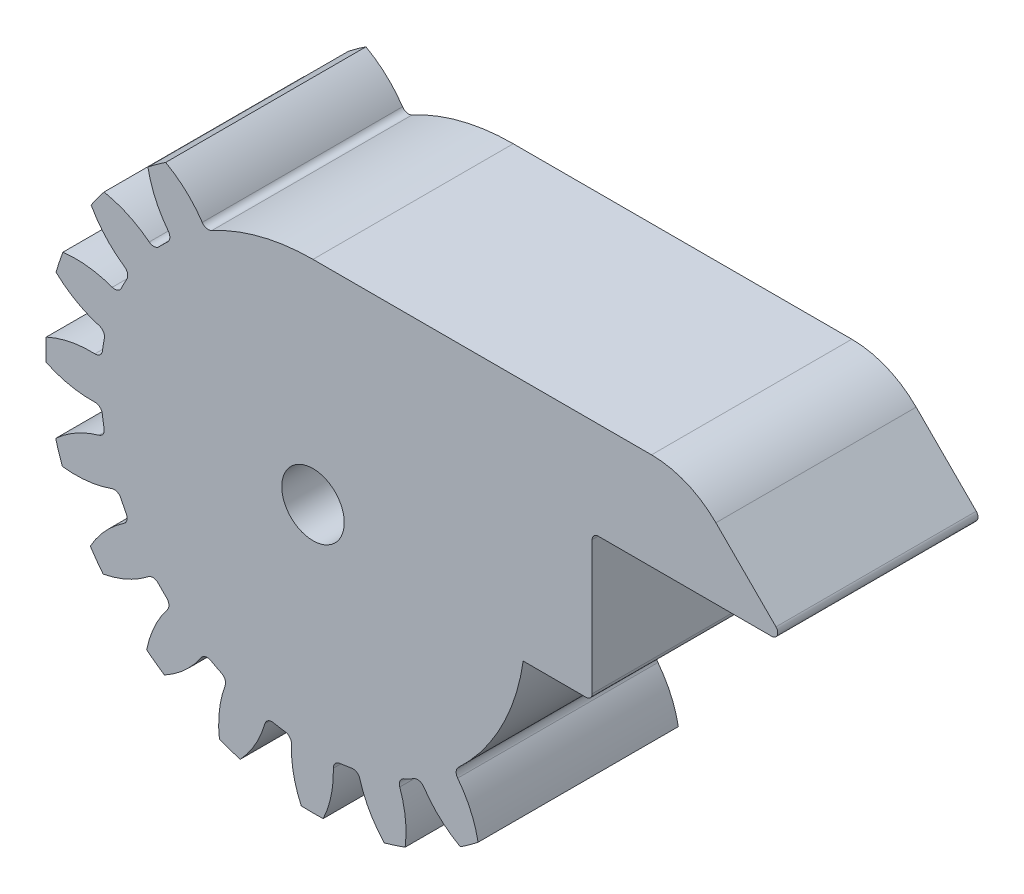
SolidWorks part; units mm, degrees
material "1023 Carbon Steel Sheet (SS)"
ref_plane "Front Plane" through (0, 0, 0) normal (0, 0, 1) x (1, 0, 0)
ref_plane "Top Plane" through (0, 0, 0) normal (0, 1, 0) x (1, 0, 0)
ref_plane "Right Plane" through (0, 0, 0) normal (1, 0, 0) x (0, 0, -1)
sketch "skBase" plane through (0, 0, 0) normal (0, 0, 1) x (1, 0, 0)
  circle A0 centre (0, 0) radius 20
  circle A1 centre (0, 0) radius 22
  circle A2 centre (0, 0) radius 17.5
  dimension "D1" = 40
  dimension "D3" = 4.5
extrude "Base" add sketch "skBase" along normal mid plane 16.5 contours A1
sketch "skToothProfile" plane through (0, 0, 0) normal (0, 0, 1) x (1, 0, 0)
  line L0 (0, 0) -> (0, 22) construction
  line L1 (-1.5692, 19.9383) -> (1.5692, 19.9383) construction
  line L2 (-1.0563, 17.4681) -> (0, 0) construction
  line L3 (0, 15.6271) -> (-2.6287, 22.8493) construction
  line L4 (0, 0) -> (3.4416, 21.7291) construction
  line L5 (1.5692, 19.9383) -> (4.6689, 19.4474) construction
  circle A0 centre (0, 0) radius 22 construction
  arc A1 (-1.0563, 17.4681) -> (-3.258, 22.7681) centre (-9.8105, 16.9387) ccw
  arc A2 (1.0563, 17.4681) -> (3.258, 22.7681) centre (9.8105, 16.9387) cw
  circle A3 centre (0, 0) radius 17.5 construction
  arc A4 (1.0563, 17.4681) -> (-1.0563, 17.4681) centre (0, 0) ccw
  circle A5 centre (0, 0) radius 20 construction
  circle A6 centre (0, 0) radius 22 construction
  circle A7 centre (0, 0) radius 23
  arc A8 (3.258, 22.7681) -> (-3.258, 22.7681) centre (0, 0) ccw
  dimension "D2" = 20
  dimension "D3" = 9
extrude "ToothProfile" cut sketch "skToothProfile" against normal through all and the other way through all
fillet "FilletToothProfile" radius 0.6 2 edges at (1.0563, 17.4681, 0) (-1.0563, 17.4681, 0)
pattern_circular "CirPatternTeeth" count 20 over 360 about axis through (0, 0, 8.25) along (0, 0, 1) of "ToothProfile", "FilletToothProfile"
sketch "skChaveta" plane through (0, 0, 8.25) normal (0, 0, 1) x (1, 0, 0)
  line L0 (0, 2.575) -> (0, 0) construction
  circle A0 centre (0, 0) radius 2.575
  dimension "D1" = 5.15
extrude "Chaveta" cut sketch "skChaveta" against normal through all contours A0
sketch "skRebaixo" plane through (0, 0, 8.25) normal (0, 0, 1) x (1, 0, 0)
  circle A0 centre (0, 0) radius 21.5
  circle A1 centre (0, 0) radius 7.5
  dimension "D1" = 43
  dimension "D2" = 15
sketch "Sketch4" plane through (0, 0, -8.25) normal (0, 0, -1) x (-1, 0, 0)
  circle A0 centre (0, 0) radius 17.5
  arc A5 (-2.5459, 21.8522) -> (-4.3314, 21.5694) centre (0, 0) ccw
  arc A6 (-2.5459, 21.8522) -> (-4.3314, 21.5694) centre (0, 0) ccw
  arc A7 (-18.0189, -1.107) -> (-21.8522, -2.5459) centre (-16.9387, -9.8105) ccw
  arc A8 (-18.0189, -1.107) -> (-21.8522, -2.5459) centre (-16.9387, -9.8105) ccw
  arc A9 (-21.5694, -4.3314) -> (-17.4791, -4.5153) centre (-19.1413, 4.096) ccw
  arc A10 (-21.5694, -4.3314) -> (-17.4791, -4.5153) centre (-19.1413, 4.096) ccw
  arc A127 (-19.996, -9.174) -> (-19.1752, -10.7848) centre (0, 0) ccw
  arc A128 (-19.996, -9.174) -> (-19.1752, -10.7848) centre (0, 0) ccw
  arc A129 (-16.1824, -14.904) -> (-14.904, -16.1824) centre (0, 0) ccw
  arc A130 (-16.1824, -14.904) -> (-14.904, -16.1824) centre (0, 0) ccw
  arc A131 (-10.7848, -19.1752) -> (-9.174, -19.996) centre (0, 0) ccw
  arc A132 (-10.7848, -19.1752) -> (-9.174, -19.996) centre (0, 0) ccw
  arc A133 (-4.3314, -21.5694) -> (-2.5459, -21.8522) centre (0, 0) ccw
  arc A134 (-4.3314, -21.5694) -> (-2.5459, -21.8522) centre (0, 0) ccw
  arc A135 (2.5459, -21.8522) -> (4.3314, -21.5694) centre (0, 0) ccw
  arc A136 (2.5459, -21.8522) -> (4.3314, -21.5694) centre (0, 0) ccw
  arc A137 (9.174, -19.996) -> (10.7848, -19.1752) centre (0, 0) ccw
  arc A138 (9.174, -19.996) -> (10.7848, -19.1752) centre (0, 0) ccw
  arc A139 (14.904, -16.1824) -> (16.1824, -14.904) centre (0, 0) ccw
  arc A140 (14.904, -16.1824) -> (16.1824, -14.904) centre (0, 0) ccw
  arc A141 (19.1752, -10.7848) -> (19.996, -9.174) centre (0, 0) ccw
  arc A142 (19.1752, -10.7848) -> (19.996, -9.174) centre (0, 0) ccw
  arc A143 (21.5694, -4.3314) -> (21.8522, -2.5459) centre (0, 0) ccw
  arc A144 (21.5694, -4.3314) -> (21.8522, -2.5459) centre (0, 0) ccw
  arc A145 (21.8522, 2.5459) -> (21.5694, 4.3314) centre (0, 0) ccw
  arc A146 (21.8522, 2.5459) -> (21.5694, 4.3314) centre (0, 0) ccw
  arc A147 (19.996, 9.174) -> (19.1752, 10.7848) centre (0, 0) ccw
  arc A148 (19.996, 9.174) -> (19.1752, 10.7848) centre (0, 0) ccw
  arc A149 (16.1824, 14.904) -> (14.904, 16.1824) centre (0, 0) ccw
  arc A150 (16.1824, 14.904) -> (14.904, 16.1824) centre (0, 0) ccw
  arc A151 (10.7848, 19.1752) -> (9.174, 19.996) centre (0, 0) ccw
  arc A152 (10.7848, 19.1752) -> (9.174, 19.996) centre (0, 0) ccw
  arc A153 (4.3314, 21.5694) -> (2.5459, 21.8522) centre (0, 0) ccw
  arc A154 (4.3314, 21.5694) -> (2.5459, 21.8522) centre (0, 0) ccw
  arc A155 (-9.174, 19.996) -> (-10.7848, 19.1752) centre (0, 0) ccw
  arc A156 (-9.174, 19.996) -> (-10.7848, 19.1752) centre (0, 0) ccw
  arc A157 (-14.904, 16.1824) -> (-16.1824, 14.904) centre (0, 0) ccw
  arc A158 (-14.904, 16.1824) -> (-16.1824, 14.904) centre (0, 0) ccw
  arc A159 (-19.1752, 10.7848) -> (-19.996, 9.174) centre (0, 0) ccw
  arc A160 (-19.1752, 10.7848) -> (-19.996, 9.174) centre (0, 0) ccw
  arc A161 (-21.5694, 4.3314) -> (-21.8522, 2.5459) centre (0, 0) ccw
  arc A162 (-21.5694, 4.3314) -> (-21.8522, 2.5459) centre (0, 0) ccw
  arc A163 (-4.3314, 21.5694) -> (-4.5153, 17.4791) centre (4.096, 19.1413) ccw
  arc A164 (-4.3314, 21.5694) -> (-4.5153, 17.4791) centre (4.096, 19.1413) ccw
  arc A165 (-4.9352, 16.7897) -> (-4.5153, 17.4791) centre (-5.1044, 17.3653) ccw
  arc A166 (-4.9352, 16.7897) -> (-4.5153, 17.4791) centre (-5.1044, 17.3653) ccw
  arc A167 (-4.9352, 16.7897) -> (-5.8761, 16.484) centre (0, 0) ccw
  arc A168 (-4.9352, 16.7897) -> (-5.8761, 16.484) centre (0, 0) ccw
  arc A169 (-6.621, 16.7949) -> (-5.8761, 16.484) centre (-6.0775, 17.0492) ccw
  arc A170 (-6.621, 16.7949) -> (-5.8761, 16.484) centre (-6.0775, 17.0492) ccw
  arc A171 (-6.621, 16.7949) -> (-9.174, 19.996) centre (-14.5647, 13.0781) ccw
  arc A172 (-6.621, 16.7949) -> (-9.174, 19.996) centre (-14.5647, 13.0781) ccw
  arc A173 (-10.7848, 19.1752) -> (-9.6956, 15.2283) centre (-2.0195, 19.4702) ccw
  arc A174 (-10.7848, 19.1752) -> (-9.6956, 15.2283) centre (-2.0195, 19.4702) ccw
  arc A175 (-9.882, 14.4429) -> (-9.6956, 15.2283) centre (-10.2208, 14.9381) ccw
  arc A176 (-9.882, 14.4429) -> (-9.6956, 15.2283) centre (-10.2208, 14.9381) ccw
  arc A177 (-9.882, 14.4429) -> (-10.6823, 13.8614) centre (0, 0) ccw
  arc A178 (-9.882, 14.4429) -> (-10.6823, 13.8614) centre (0, 0) ccw
  arc A179 (-11.4868, 13.9269) -> (-10.6823, 13.8614) centre (-11.0486, 14.3366) ccw
  arc A180 (-11.4868, 13.9269) -> (-10.6823, 13.8614) centre (-11.0486, 14.3366) ccw
  arc A181 (-11.4868, 13.9269) -> (-14.904, 16.1824) centre (-17.8932, 7.9372) ccw
  arc A182 (-11.4868, 13.9269) -> (-14.904, 16.1824) centre (-17.8932, 7.9372) ccw
  arc A183 (-16.1824, 14.904) -> (-13.9269, 11.4868) centre (-7.9372, 17.8932) ccw
  arc A184 (-16.1824, 14.904) -> (-13.9269, 11.4868) centre (-7.9372, 17.8932) ccw
  arc A185 (-13.8614, 10.6823) -> (-13.9269, 11.4868) centre (-14.3366, 11.0486) ccw
  arc A186 (-13.8614, 10.6823) -> (-13.9269, 11.4868) centre (-14.3366, 11.0486) ccw
  arc A187 (-13.8614, 10.6823) -> (-14.4429, 9.882) centre (0, 0) ccw
  arc A188 (-13.8614, 10.6823) -> (-14.4429, 9.882) centre (0, 0) ccw
  arc A189 (-15.2283, 9.6956) -> (-14.4429, 9.882) centre (-14.9381, 10.2208) ccw
  arc A190 (-15.2283, 9.6956) -> (-14.4429, 9.882) centre (-14.9381, 10.2208) ccw
  arc A191 (-15.2283, 9.6956) -> (-19.1752, 10.7848) centre (-19.4702, 2.0195) ccw
  arc A192 (-15.2283, 9.6956) -> (-19.1752, 10.7848) centre (-19.4702, 2.0195) ccw
  arc A193 (-19.996, 9.174) -> (-16.7949, 6.621) centre (-13.0781, 14.5647) ccw
  arc A194 (-19.996, 9.174) -> (-16.7949, 6.621) centre (-13.0781, 14.5647) ccw
  arc A195 (-16.484, 5.8761) -> (-16.7949, 6.621) centre (-17.0492, 6.0775) ccw
  arc A196 (-16.484, 5.8761) -> (-16.7949, 6.621) centre (-17.0492, 6.0775) ccw
  arc A197 (-16.484, 5.8761) -> (-16.7897, 4.9352) centre (0, 0) ccw
  arc A198 (-16.484, 5.8761) -> (-16.7897, 4.9352) centre (0, 0) ccw
  arc A199 (-17.4791, 4.5153) -> (-16.7897, 4.9352) centre (-17.3653, 5.1044) ccw
  arc A200 (-17.4791, 4.5153) -> (-16.7897, 4.9352) centre (-17.3653, 5.1044) ccw
  arc A201 (-17.4791, 4.5153) -> (-21.5694, 4.3314) centre (-19.1413, -4.096) ccw
  arc A202 (-17.4791, 4.5153) -> (-21.5694, 4.3314) centre (-19.1413, -4.096) ccw
  arc A203 (-21.8522, 2.5459) -> (-18.0189, 1.107) centre (-16.9387, 9.8105) ccw
  arc A204 (-21.8522, 2.5459) -> (-18.0189, 1.107) centre (-16.9387, 9.8105) ccw
  arc A205 (-17.493, 0.4946) -> (-18.0189, 1.107) centre (-18.0928, 0.5116) ccw
  arc A206 (-17.493, 0.4946) -> (-18.0189, 1.107) centre (-18.0928, 0.5116) ccw
  arc A207 (-17.493, 0.4946) -> (-17.493, -0.4946) centre (0, 0) ccw
  arc A208 (-17.493, 0.4946) -> (-17.493, -0.4946) centre (0, 0) ccw
  arc A209 (-18.0189, -1.107) -> (-17.493, -0.4946) centre (-18.0928, -0.5116) ccw
  arc A210 (-18.0189, -1.107) -> (-17.493, -0.4946) centre (-18.0928, -0.5116) ccw
  arc A211 (-16.7897, -4.9352) -> (-17.4791, -4.5153) centre (-17.3653, -5.1044) ccw
  arc A212 (-16.7897, -4.9352) -> (-17.4791, -4.5153) centre (-17.3653, -5.1044) ccw
  arc A213 (-16.7897, -4.9352) -> (-16.484, -5.8761) centre (0, 0) ccw
  arc A214 (-16.7897, -4.9352) -> (-16.484, -5.8761) centre (0, 0) ccw
  arc A215 (-16.7949, -6.621) -> (-16.484, -5.8761) centre (-17.0492, -6.0775) ccw
  arc A216 (-16.7949, -6.621) -> (-16.484, -5.8761) centre (-17.0492, -6.0775) ccw
  arc A217 (-16.7949, -6.621) -> (-19.996, -9.174) centre (-13.0781, -14.5647) ccw
  arc A218 (-16.7949, -6.621) -> (-19.996, -9.174) centre (-13.0781, -14.5647) ccw
  arc A219 (-19.1752, -10.7848) -> (-15.2283, -9.6956) centre (-19.4702, -2.0195) ccw
  arc A220 (-19.1752, -10.7848) -> (-15.2283, -9.6956) centre (-19.4702, -2.0195) ccw
  arc A221 (-14.4429, -9.882) -> (-15.2283, -9.6956) centre (-14.9381, -10.2208) ccw
  arc A222 (-14.4429, -9.882) -> (-15.2283, -9.6956) centre (-14.9381, -10.2208) ccw
  arc A223 (-14.4429, -9.882) -> (-13.8614, -10.6823) centre (0, 0) ccw
  arc A224 (-14.4429, -9.882) -> (-13.8614, -10.6823) centre (0, 0) ccw
  arc A225 (-13.9269, -11.4868) -> (-13.8614, -10.6823) centre (-14.3366, -11.0486) ccw
  arc A226 (-13.9269, -11.4868) -> (-13.8614, -10.6823) centre (-14.3366, -11.0486) ccw
  arc A227 (-13.9269, -11.4868) -> (-16.1824, -14.904) centre (-7.9372, -17.8932) ccw
  arc A228 (-13.9269, -11.4868) -> (-16.1824, -14.904) centre (-7.9372, -17.8932) ccw
  arc A229 (-14.904, -16.1824) -> (-11.4868, -13.9269) centre (-17.8932, -7.9372) ccw
  arc A230 (-14.904, -16.1824) -> (-11.4868, -13.9269) centre (-17.8932, -7.9372) ccw
  arc A231 (-10.6823, -13.8614) -> (-11.4868, -13.9269) centre (-11.0486, -14.3366) ccw
  arc A232 (-10.6823, -13.8614) -> (-11.4868, -13.9269) centre (-11.0486, -14.3366) ccw
  arc A233 (-10.6823, -13.8614) -> (-9.882, -14.4429) centre (0, 0) ccw
  arc A234 (-10.6823, -13.8614) -> (-9.882, -14.4429) centre (0, 0) ccw
  arc A235 (-9.6956, -15.2283) -> (-9.882, -14.4429) centre (-10.2208, -14.9381) ccw
  arc A236 (-9.6956, -15.2283) -> (-9.882, -14.4429) centre (-10.2208, -14.9381) ccw
  arc A237 (-9.6956, -15.2283) -> (-10.7848, -19.1752) centre (-2.0195, -19.4702) ccw
  arc A238 (-9.6956, -15.2283) -> (-10.7848, -19.1752) centre (-2.0195, -19.4702) ccw
  arc A239 (-9.174, -19.996) -> (-6.621, -16.7949) centre (-14.5647, -13.0781) ccw
  arc A240 (-9.174, -19.996) -> (-6.621, -16.7949) centre (-14.5647, -13.0781) ccw
  arc A241 (-5.8761, -16.484) -> (-6.621, -16.7949) centre (-6.0775, -17.0492) ccw
  arc A242 (-5.8761, -16.484) -> (-6.621, -16.7949) centre (-6.0775, -17.0492) ccw
  arc A243 (-5.8761, -16.484) -> (-4.9352, -16.7897) centre (0, 0) ccw
  arc A244 (-5.8761, -16.484) -> (-4.9352, -16.7897) centre (0, 0) ccw
  arc A245 (-4.5153, -17.4791) -> (-4.9352, -16.7897) centre (-5.1044, -17.3653) ccw
  arc A246 (-4.5153, -17.4791) -> (-4.9352, -16.7897) centre (-5.1044, -17.3653) ccw
  arc A247 (-4.5153, -17.4791) -> (-4.3314, -21.5694) centre (4.096, -19.1413) ccw
  arc A248 (-4.5153, -17.4791) -> (-4.3314, -21.5694) centre (4.096, -19.1413) ccw
  arc A249 (-2.5459, -21.8522) -> (-1.107, -18.0189) centre (-9.8105, -16.9387) ccw
  arc A250 (-2.5459, -21.8522) -> (-1.107, -18.0189) centre (-9.8105, -16.9387) ccw
  arc A251 (-0.4946, -17.493) -> (-1.107, -18.0189) centre (-0.5116, -18.0928) ccw
  arc A252 (-0.4946, -17.493) -> (-1.107, -18.0189) centre (-0.5116, -18.0928) ccw
  arc A253 (-0.4946, -17.493) -> (0.4946, -17.493) centre (0, 0) ccw
  arc A254 (-0.4946, -17.493) -> (0.4946, -17.493) centre (0, 0) ccw
  arc A255 (1.107, -18.0189) -> (0.4946, -17.493) centre (0.5116, -18.0928) ccw
  arc A256 (1.107, -18.0189) -> (0.4946, -17.493) centre (0.5116, -18.0928) ccw
  arc A257 (1.107, -18.0189) -> (2.5459, -21.8522) centre (9.8105, -16.9387) ccw
  arc A258 (1.107, -18.0189) -> (2.5459, -21.8522) centre (9.8105, -16.9387) ccw
  arc A259 (4.3314, -21.5694) -> (4.5153, -17.4791) centre (-4.096, -19.1413) ccw
  arc A260 (4.3314, -21.5694) -> (4.5153, -17.4791) centre (-4.096, -19.1413) ccw
  arc A261 (4.9352, -16.7897) -> (4.5153, -17.4791) centre (5.1044, -17.3653) ccw
  arc A262 (4.9352, -16.7897) -> (4.5153, -17.4791) centre (5.1044, -17.3653) ccw
  arc A263 (4.9352, -16.7897) -> (5.8761, -16.484) centre (0, 0) ccw
  arc A264 (4.9352, -16.7897) -> (5.8761, -16.484) centre (0, 0) ccw
  arc A265 (6.621, -16.7949) -> (5.8761, -16.484) centre (6.0775, -17.0492) ccw
  arc A266 (6.621, -16.7949) -> (5.8761, -16.484) centre (6.0775, -17.0492) ccw
  arc A267 (6.621, -16.7949) -> (9.174, -19.996) centre (14.5647, -13.0781) ccw
  arc A268 (6.621, -16.7949) -> (9.174, -19.996) centre (14.5647, -13.0781) ccw
  arc A269 (10.7848, -19.1752) -> (9.6956, -15.2283) centre (2.0195, -19.4702) ccw
  arc A270 (10.7848, -19.1752) -> (9.6956, -15.2283) centre (2.0195, -19.4702) ccw
  arc A271 (9.882, -14.4429) -> (9.6956, -15.2283) centre (10.2208, -14.9381) ccw
  arc A272 (9.882, -14.4429) -> (9.6956, -15.2283) centre (10.2208, -14.9381) ccw
  arc A273 (9.882, -14.4429) -> (10.6823, -13.8614) centre (0, 0) ccw
  arc A274 (9.882, -14.4429) -> (10.6823, -13.8614) centre (0, 0) ccw
  arc A275 (11.4868, -13.9269) -> (10.6823, -13.8614) centre (11.0486, -14.3366) ccw
  arc A276 (11.4868, -13.9269) -> (10.6823, -13.8614) centre (11.0486, -14.3366) ccw
  arc A277 (11.4868, -13.9269) -> (14.904, -16.1824) centre (17.8932, -7.9372) ccw
  arc A278 (11.4868, -13.9269) -> (14.904, -16.1824) centre (17.8932, -7.9372) ccw
  arc A279 (16.1824, -14.904) -> (13.9269, -11.4868) centre (7.9372, -17.8932) ccw
  arc A280 (16.1824, -14.904) -> (13.9269, -11.4868) centre (7.9372, -17.8932) ccw
  arc A281 (13.8614, -10.6823) -> (13.9269, -11.4868) centre (14.3366, -11.0486) ccw
  arc A282 (13.8614, -10.6823) -> (13.9269, -11.4868) centre (14.3366, -11.0486) ccw
  arc A283 (13.8614, -10.6823) -> (14.4429, -9.882) centre (0, 0) ccw
  arc A284 (13.8614, -10.6823) -> (14.4429, -9.882) centre (0, 0) ccw
  arc A285 (15.2283, -9.6956) -> (14.4429, -9.882) centre (14.9381, -10.2208) ccw
  arc A286 (15.2283, -9.6956) -> (14.4429, -9.882) centre (14.9381, -10.2208) ccw
  arc A287 (15.2283, -9.6956) -> (19.1752, -10.7848) centre (19.4702, -2.0195) ccw
  arc A288 (15.2283, -9.6956) -> (19.1752, -10.7848) centre (19.4702, -2.0195) ccw
  arc A289 (19.996, -9.174) -> (16.7949, -6.621) centre (13.0781, -14.5647) ccw
  arc A290 (19.996, -9.174) -> (16.7949, -6.621) centre (13.0781, -14.5647) ccw
  arc A291 (16.484, -5.8761) -> (16.7949, -6.621) centre (17.0492, -6.0775) ccw
  arc A292 (16.484, -5.8761) -> (16.7949, -6.621) centre (17.0492, -6.0775) ccw
  arc A293 (16.484, -5.8761) -> (16.7897, -4.9352) centre (0, 0) ccw
  arc A294 (16.484, -5.8761) -> (16.7897, -4.9352) centre (0, 0) ccw
  arc A295 (17.4791, -4.5153) -> (16.7897, -4.9352) centre (17.3653, -5.1044) ccw
  arc A296 (17.4791, -4.5153) -> (16.7897, -4.9352) centre (17.3653, -5.1044) ccw
  arc A297 (17.4791, -4.5153) -> (21.5694, -4.3314) centre (19.1413, 4.096) ccw
  arc A298 (17.4791, -4.5153) -> (21.5694, -4.3314) centre (19.1413, 4.096) ccw
  arc A299 (21.8522, -2.5459) -> (18.0189, -1.107) centre (16.9387, -9.8105) ccw
  arc A300 (21.8522, -2.5459) -> (18.0189, -1.107) centre (16.9387, -9.8105) ccw
  arc A301 (17.493, -0.4946) -> (18.0189, -1.107) centre (18.0928, -0.5116) ccw
  arc A302 (17.493, -0.4946) -> (18.0189, -1.107) centre (18.0928, -0.5116) ccw
  arc A303 (17.493, -0.4946) -> (17.493, 0.4946) centre (0, 0) ccw
  arc A304 (17.493, -0.4946) -> (17.493, 0.4946) centre (0, 0) ccw
  arc A305 (18.0189, 1.107) -> (17.493, 0.4946) centre (18.0928, 0.5116) ccw
  arc A306 (18.0189, 1.107) -> (17.493, 0.4946) centre (18.0928, 0.5116) ccw
  arc A307 (18.0189, 1.107) -> (21.8522, 2.5459) centre (16.9387, 9.8105) ccw
  arc A308 (18.0189, 1.107) -> (21.8522, 2.5459) centre (16.9387, 9.8105) ccw
  arc A309 (21.5694, 4.3314) -> (17.4791, 4.5153) centre (19.1413, -4.096) ccw
  arc A310 (21.5694, 4.3314) -> (17.4791, 4.5153) centre (19.1413, -4.096) ccw
  arc A311 (-21.8522, -2.5459) -> (-21.5694, -4.3314) centre (0, 0) ccw
  arc A312 (-21.8522, -2.5459) -> (-21.5694, -4.3314) centre (0, 0) ccw
  arc A313 (16.7897, 4.9352) -> (17.4791, 4.5153) centre (17.3653, 5.1044) ccw
  arc A314 (16.7897, 4.9352) -> (17.4791, 4.5153) centre (17.3653, 5.1044) ccw
  arc A315 (16.7897, 4.9352) -> (16.484, 5.8761) centre (0, 0) ccw
  arc A316 (16.7897, 4.9352) -> (16.484, 5.8761) centre (0, 0) ccw
  arc A317 (16.7949, 6.621) -> (16.484, 5.8761) centre (17.0492, 6.0775) ccw
  arc A318 (16.7949, 6.621) -> (16.484, 5.8761) centre (17.0492, 6.0775) ccw
  arc A319 (16.7949, 6.621) -> (19.996, 9.174) centre (13.0781, 14.5647) ccw
  arc A320 (16.7949, 6.621) -> (19.996, 9.174) centre (13.0781, 14.5647) ccw
  arc A321 (19.1752, 10.7848) -> (15.2283, 9.6956) centre (19.4702, 2.0195) ccw
  arc A322 (19.1752, 10.7848) -> (15.2283, 9.6956) centre (19.4702, 2.0195) ccw
  arc A323 (14.4429, 9.882) -> (15.2283, 9.6956) centre (14.9381, 10.2208) ccw
  arc A324 (14.4429, 9.882) -> (15.2283, 9.6956) centre (14.9381, 10.2208) ccw
  arc A325 (14.4429, 9.882) -> (13.8614, 10.6823) centre (0, 0) ccw
  arc A326 (14.4429, 9.882) -> (13.8614, 10.6823) centre (0, 0) ccw
  arc A327 (13.9269, 11.4868) -> (13.8614, 10.6823) centre (14.3366, 11.0486) ccw
  arc A328 (13.9269, 11.4868) -> (13.8614, 10.6823) centre (14.3366, 11.0486) ccw
  arc A329 (13.9269, 11.4868) -> (16.1824, 14.904) centre (7.9372, 17.8932) ccw
  arc A330 (13.9269, 11.4868) -> (16.1824, 14.904) centre (7.9372, 17.8932) ccw
  arc A331 (14.904, 16.1824) -> (11.4868, 13.9269) centre (17.8932, 7.9372) ccw
  arc A332 (14.904, 16.1824) -> (11.4868, 13.9269) centre (17.8932, 7.9372) ccw
  arc A333 (10.6823, 13.8614) -> (11.4868, 13.9269) centre (11.0486, 14.3366) ccw
  arc A334 (10.6823, 13.8614) -> (11.4868, 13.9269) centre (11.0486, 14.3366) ccw
  arc A335 (10.6823, 13.8614) -> (9.882, 14.4429) centre (0, 0) ccw
  arc A336 (10.6823, 13.8614) -> (9.882, 14.4429) centre (0, 0) ccw
  arc A337 (9.6956, 15.2283) -> (9.882, 14.4429) centre (10.2208, 14.9381) ccw
  arc A338 (9.6956, 15.2283) -> (9.882, 14.4429) centre (10.2208, 14.9381) ccw
  arc A339 (9.6956, 15.2283) -> (10.7848, 19.1752) centre (2.0195, 19.4702) ccw
  arc A340 (9.6956, 15.2283) -> (10.7848, 19.1752) centre (2.0195, 19.4702) ccw
  arc A341 (9.174, 19.996) -> (6.621, 16.7949) centre (14.5647, 13.0781) ccw
  arc A342 (9.174, 19.996) -> (6.621, 16.7949) centre (14.5647, 13.0781) ccw
  arc A343 (5.8761, 16.484) -> (6.621, 16.7949) centre (6.0775, 17.0492) ccw
  arc A344 (5.8761, 16.484) -> (6.621, 16.7949) centre (6.0775, 17.0492) ccw
  arc A345 (5.8761, 16.484) -> (4.9352, 16.7897) centre (0, 0) ccw
  arc A346 (5.8761, 16.484) -> (4.9352, 16.7897) centre (0, 0) ccw
  arc A347 (4.5153, 17.4791) -> (4.9352, 16.7897) centre (5.1044, 17.3653) ccw
  arc A348 (4.5153, 17.4791) -> (4.9352, 16.7897) centre (5.1044, 17.3653) ccw
  arc A349 (4.5153, 17.4791) -> (4.3314, 21.5694) centre (-4.096, 19.1413) ccw
  arc A350 (4.5153, 17.4791) -> (4.3314, 21.5694) centre (-4.096, 19.1413) ccw
  arc A351 (2.5459, 21.8522) -> (1.107, 18.0189) centre (9.8105, 16.9387) ccw
  arc A352 (2.5459, 21.8522) -> (1.107, 18.0189) centre (9.8105, 16.9387) ccw
  arc A353 (0.4946, 17.493) -> (1.107, 18.0189) centre (0.5116, 18.0928) ccw
  arc A354 (0.4946, 17.493) -> (1.107, 18.0189) centre (0.5116, 18.0928) ccw
  arc A355 (0.4946, 17.493) -> (-0.4946, 17.493) centre (0, 0) ccw
  arc A356 (0.4946, 17.493) -> (-0.4946, 17.493) centre (0, 0) ccw
  arc A357 (-1.107, 18.0189) -> (-0.4946, 17.493) centre (-0.5116, 18.0928) ccw
  arc A358 (-1.107, 18.0189) -> (-0.4946, 17.493) centre (-0.5116, 18.0928) ccw
  arc A359 (-1.107, 18.0189) -> (-2.5459, 21.8522) centre (-9.8105, 16.9387) ccw
  arc A360 (-1.107, 18.0189) -> (-2.5459, 21.8522) centre (-9.8105, 16.9387) ccw
  dimension "D1" = 0
sketch "Sketch6" plane through (0, 0, -8.25) normal (0, 0, -1) x (-1, 0, 0)
  circle A0 centre (0, 0) radius 20 construction
  dimension "D1" = 40
move or copy body "Body-Move/Copy1" bodies to move or copy 104 copy no rotation origin (0, 0, 0) rotation axis (0, 0, 1) rotation angle 8.84
sketch "Sketch7" plane through (0, 0, -8.25) normal (0, 0, -1) x (-1, 0, 0)
  circle A0 centre (0, 0) radius 17.5
  arc A120 (0.8425, 21.9839) -> (-0.9653, 21.9788) centre (0, 0) ccw
  arc A121 (-0.9653, 21.9788) -> (-1.7755, 17.9653) centre (6.9889, 18.2845) ccw
  arc A122 (-2.2964, 17.3487) -> (-1.7755, 17.9653) centre (-2.3751, 17.9435) ccw
  arc A123 (-2.2964, 17.3487) -> (-3.2731, 17.1912) centre (0, 0) ccw
  arc A124 (-3.9614, 17.6129) -> (-3.2731, 17.1912) centre (-3.3853, 17.7806) ccw
  arc A125 (-3.9614, 17.6129) -> (-5.9921, 21.1683) centre (-12.3819, 15.161) ccw
  arc A126 (-5.9921, 21.1683) -> (-7.7099, 20.6048) centre (0, 0) ccw
  arc A127 (-7.7099, 20.6048) -> (-7.2402, 16.5374) centre (0.9966, 19.5493) ccw
  arc A128 (-7.545, 15.7899) -> (-7.2402, 16.5374) centre (-7.8037, 16.3313) ccw
  arc A129 (-7.545, 15.7899) -> (-8.4253, 15.3384) centre (0, 0) ccw
  arc A130 (-9.2102, 15.5267) -> (-8.4253, 15.3384) centre (-8.7141, 15.8642) ccw
  arc A131 (-9.2102, 15.5267) -> (-12.2402, 18.2805) centre (-16.4609, 10.5927) ccw
  arc A132 (-12.2402, 18.2805) -> (-13.6998, 17.2138) centre (0, 0) ccw
  arc A133 (-13.6998, 17.2138) -> (-11.9962, 13.4906) centre (-5.0932, 18.9004) ccw
  arc A134 (-12.0551, 12.6856) -> (-11.9962, 13.4906) centre (-12.4684, 13.1205) ccw
  arc A135 (-12.0551, 12.6856) -> (-12.7527, 11.9841) centre (0, 0) ccw
  arc A136 (-13.5574, 11.9207) -> (-12.7527, 11.9841) centre (-13.1899, 12.395) ccw
  arc A137 (-13.5574, 11.9207) -> (-17.2901, 13.6034) centre (-18.9286, 4.9876) ccw
  arc A138 (-17.2901, 13.6034) -> (-18.3486, 12.1379) centre (0, 0) ccw
  arc A139 (-18.3486, 12.1379) -> (-15.5779, 9.1233) centre (-10.6845, 16.4015) ccw
  arc A140 (-15.3852, 8.3395) -> (-15.5779, 9.1233) centre (-15.9127, 8.6254) ccw
  arc A141 (-15.3852, 8.3395) -> (-15.8318, 7.4567) centre (0, 0) ccw
  arc A142 (-16.5775, 7.1478) -> (-15.8318, 7.4567) centre (-16.3746, 7.7124) ccw
  arc A143 (-16.5775, 7.1478) -> (-20.6475, 7.5947) centre (-19.5434, -1.1058) ccw
  arc A144 (-20.6475, 7.5947) -> (-21.2014, 5.8738) centre (0, 0) ccw
  arc A145 (-21.2014, 5.8738) -> (-17.6347, 3.863) centre (-15.2299, 12.2971) ccw
  arc A146 (-17.2092, 3.177) -> (-17.6347, 3.863) centre (-17.7992, 3.2859) ccw
  arc A147 (-17.2092, 3.177) -> (-17.3612, 2.1995) centre (0, 0) ccw
  arc A148 (-17.975, 1.6752) -> (-17.3612, 2.1995) centre (-17.9565, 2.2749) ccw
  arc A149 (-17.975, 1.6752) -> (-21.9839, 0.8425) centre (-18.2452, -7.0909) ccw
  arc A150 (-21.9839, 0.8425) -> (-21.9788, -0.9653) centre (0, 0) ccw
  arc A151 (-21.9788, -0.9653) -> (-17.9653, -1.7755) centre (-18.2845, 6.9889) ccw
  arc A152 (-17.3487, -2.2964) -> (-17.9653, -1.7755) centre (-17.9435, -2.3751) ccw
  arc A153 (-17.3487, -2.2964) -> (-17.1912, -3.2731) centre (0, 0) ccw
  arc A154 (-17.6129, -3.9614) -> (-17.1912, -3.2731) centre (-17.7806, -3.3853) ccw
  arc A155 (-17.6129, -3.9614) -> (-21.1683, -5.9921) centre (-15.161, -12.3819) ccw
  arc A156 (-21.1683, -5.9921) -> (-20.6048, -7.7099) centre (0, 0) ccw
  arc A157 (-20.6048, -7.7099) -> (-16.5374, -7.2402) centre (-19.5493, 0.9966) ccw
  arc A158 (-15.7899, -7.545) -> (-16.5374, -7.2402) centre (-16.3313, -7.8037) ccw
  arc A159 (-15.7899, -7.545) -> (-15.3384, -8.4253) centre (0, 0) ccw
  arc A160 (-15.5267, -9.2102) -> (-15.3384, -8.4253) centre (-15.8642, -8.7141) ccw
  arc A161 (-15.5267, -9.2102) -> (-18.2805, -12.2402) centre (-10.5927, -16.4609) ccw
  arc A162 (-18.2805, -12.2402) -> (-17.2138, -13.6998) centre (0, 0) ccw
  arc A163 (-17.2138, -13.6998) -> (-13.4906, -11.9962) centre (-18.9004, -5.0932) ccw
  arc A164 (-12.6856, -12.0551) -> (-13.4906, -11.9962) centre (-13.1205, -12.4684) ccw
  arc A165 (-12.6856, -12.0551) -> (-11.9841, -12.7527) centre (0, 0) ccw
  arc A166 (-11.9207, -13.5574) -> (-11.9841, -12.7527) centre (-12.395, -13.1899) ccw
  arc A167 (-11.9207, -13.5574) -> (-13.6034, -17.2901) centre (-4.9876, -18.9286) ccw
  arc A168 (-13.6034, -17.2901) -> (-12.1379, -18.3486) centre (0, 0) ccw
  arc A169 (-12.1379, -18.3486) -> (-9.1233, -15.5779) centre (-16.4015, -10.6845) ccw
  arc A170 (-8.3395, -15.3852) -> (-9.1233, -15.5779) centre (-8.6254, -15.9127) ccw
  arc A171 (-8.3395, -15.3852) -> (-7.4567, -15.8318) centre (0, 0) ccw
  arc A172 (-7.1478, -16.5775) -> (-7.4567, -15.8318) centre (-7.7124, -16.3746) ccw
  arc A173 (-7.1478, -16.5775) -> (-7.5947, -20.6475) centre (1.1058, -19.5434) ccw
  arc A174 (-7.5947, -20.6475) -> (-5.8738, -21.2014) centre (0, 0) ccw
  arc A175 (-5.8738, -21.2014) -> (-3.863, -17.6347) centre (-12.2971, -15.2299) ccw
  arc A176 (-3.177, -17.2092) -> (-3.863, -17.6347) centre (-3.2859, -17.7992) ccw
  arc A177 (-3.177, -17.2092) -> (-2.1995, -17.3612) centre (0, 0) ccw
  arc A178 (-1.6752, -17.975) -> (-2.1995, -17.3612) centre (-2.2749, -17.9565) ccw
  arc A179 (-1.6752, -17.975) -> (-0.8425, -21.9839) centre (7.0909, -18.2452) ccw
  arc A180 (-0.8425, -21.9839) -> (0.9653, -21.9788) centre (0, 0) ccw
  arc A181 (0.9653, -21.9788) -> (1.7755, -17.9653) centre (-6.9889, -18.2845) ccw
  arc A182 (2.2964, -17.3487) -> (1.7755, -17.9653) centre (2.3751, -17.9435) ccw
  arc A183 (2.2964, -17.3487) -> (3.2731, -17.1912) centre (0, 0) ccw
  arc A184 (3.9614, -17.6129) -> (3.2731, -17.1912) centre (3.3853, -17.7806) ccw
  arc A185 (3.9614, -17.6129) -> (5.9921, -21.1683) centre (12.3819, -15.161) ccw
  arc A186 (5.9921, -21.1683) -> (7.7099, -20.6048) centre (0, 0) ccw
  arc A187 (7.7099, -20.6048) -> (7.2402, -16.5374) centre (-0.9966, -19.5493) ccw
  arc A188 (7.545, -15.7899) -> (7.2402, -16.5374) centre (7.8037, -16.3313) ccw
  arc A189 (7.545, -15.7899) -> (8.4253, -15.3384) centre (0, 0) ccw
  arc A190 (9.2102, -15.5267) -> (8.4253, -15.3384) centre (8.7141, -15.8642) ccw
  arc A191 (9.2102, -15.5267) -> (12.2402, -18.2805) centre (16.4609, -10.5927) ccw
  arc A192 (12.2402, -18.2805) -> (13.6998, -17.2138) centre (0, 0) ccw
  arc A193 (13.6998, -17.2138) -> (11.9962, -13.4906) centre (5.0932, -18.9004) ccw
  arc A194 (12.0551, -12.6856) -> (11.9962, -13.4906) centre (12.4684, -13.1205) ccw
  arc A195 (12.0551, -12.6856) -> (12.7527, -11.9841) centre (0, 0) ccw
  arc A196 (13.5574, -11.9207) -> (12.7527, -11.9841) centre (13.1899, -12.395) ccw
  arc A197 (13.5574, -11.9207) -> (17.2901, -13.6034) centre (18.9286, -4.9876) ccw
  arc A198 (17.2901, -13.6034) -> (18.3486, -12.1379) centre (0, 0) ccw
  arc A199 (18.3486, -12.1379) -> (15.5779, -9.1233) centre (10.6845, -16.4015) ccw
  arc A200 (15.3852, -8.3395) -> (15.5779, -9.1233) centre (15.9127, -8.6254) ccw
  arc A201 (15.3852, -8.3395) -> (15.8318, -7.4567) centre (0, 0) ccw
  arc A202 (16.5775, -7.1478) -> (15.8318, -7.4567) centre (16.3746, -7.7124) ccw
  arc A203 (16.5775, -7.1478) -> (20.6475, -7.5947) centre (19.5434, 1.1058) ccw
  arc A204 (20.6475, -7.5947) -> (21.2014, -5.8738) centre (0, 0) ccw
  arc A205 (21.2014, -5.8738) -> (17.6347, -3.863) centre (15.2299, -12.2971) ccw
  arc A206 (17.2092, -3.177) -> (17.6347, -3.863) centre (17.7992, -3.2859) ccw
  arc A207 (17.2092, -3.177) -> (17.3612, -2.1995) centre (0, 0) ccw
  arc A208 (17.975, -1.6752) -> (17.3612, -2.1995) centre (17.9565, -2.2749) ccw
  arc A209 (17.975, -1.6752) -> (21.9839, -0.8425) centre (18.2452, 7.0909) ccw
  arc A210 (21.9839, -0.8425) -> (21.9788, 0.9653) centre (0, 0) ccw
  arc A211 (21.9788, 0.9653) -> (17.9653, 1.7755) centre (18.2845, -6.9889) ccw
  arc A212 (17.3487, 2.2964) -> (17.9653, 1.7755) centre (17.9435, 2.3751) ccw
  arc A213 (17.3487, 2.2964) -> (17.1912, 3.2731) centre (0, 0) ccw
  arc A214 (17.6129, 3.9614) -> (17.1912, 3.2731) centre (17.7806, 3.3853) ccw
  arc A215 (17.6129, 3.9614) -> (21.1683, 5.9921) centre (15.161, 12.3819) ccw
  arc A216 (21.1683, 5.9921) -> (20.6048, 7.7099) centre (0, 0) ccw
  arc A217 (20.6048, 7.7099) -> (16.5374, 7.2402) centre (19.5493, -0.9966) ccw
  arc A218 (15.7899, 7.545) -> (16.5374, 7.2402) centre (16.3313, 7.8037) ccw
  arc A219 (15.7899, 7.545) -> (15.3384, 8.4253) centre (0, 0) ccw
  arc A220 (15.5267, 9.2102) -> (15.3384, 8.4253) centre (15.8642, 8.7141) ccw
  arc A221 (15.5267, 9.2102) -> (18.2805, 12.2402) centre (10.5927, 16.4609) ccw
  arc A222 (18.2805, 12.2402) -> (17.2138, 13.6998) centre (0, 0) ccw
  arc A223 (17.2138, 13.6998) -> (13.4906, 11.9962) centre (18.9004, 5.0932) ccw
  arc A224 (12.6856, 12.0551) -> (13.4906, 11.9962) centre (13.1205, 12.4684) ccw
  arc A225 (12.6856, 12.0551) -> (11.9841, 12.7527) centre (0, 0) ccw
  arc A226 (11.9207, 13.5574) -> (11.9841, 12.7527) centre (12.395, 13.1899) ccw
  arc A227 (11.9207, 13.5574) -> (13.6034, 17.2901) centre (4.9876, 18.9286) ccw
  arc A228 (13.6034, 17.2901) -> (12.1379, 18.3486) centre (0, 0) ccw
  arc A229 (12.1379, 18.3486) -> (9.1233, 15.5779) centre (16.4015, 10.6845) ccw
  arc A230 (8.3395, 15.3852) -> (9.1233, 15.5779) centre (8.6254, 15.9127) ccw
  arc A231 (8.3395, 15.3852) -> (7.4567, 15.8318) centre (0, 0) ccw
  arc A232 (7.1478, 16.5775) -> (7.4567, 15.8318) centre (7.7124, 16.3746) ccw
  arc A233 (7.1478, 16.5775) -> (7.5947, 20.6475) centre (-1.1058, 19.5434) ccw
  arc A234 (7.5947, 20.6475) -> (5.8738, 21.2014) centre (0, 0) ccw
  arc A235 (5.8738, 21.2014) -> (3.863, 17.6347) centre (12.2971, 15.2299) ccw
  arc A236 (3.177, 17.2092) -> (3.863, 17.6347) centre (3.2859, 17.7992) ccw
  arc A237 (3.177, 17.2092) -> (2.1995, 17.3612) centre (0, 0) ccw
  arc A238 (1.6752, 17.975) -> (2.1995, 17.3612) centre (2.2749, 17.9565) ccw
  arc A239 (1.6752, 17.975) -> (0.8425, 21.9839) centre (-7.0909, 18.2452) ccw
  arc A240 (0.8425, 21.9839) -> (-0.9653, 21.9788) centre (0, 0) ccw
  arc A241 (-0.9653, 21.9788) -> (-1.7755, 17.9653) centre (6.9889, 18.2845) ccw
  arc A242 (-2.2964, 17.3487) -> (-1.7755, 17.9653) centre (-2.3751, 17.9435) ccw
  arc A243 (-2.2964, 17.3487) -> (-3.2731, 17.1912) centre (0, 0) ccw
  arc A244 (-3.9614, 17.6129) -> (-3.2731, 17.1912) centre (-3.3853, 17.7806) ccw
  arc A245 (-3.9614, 17.6129) -> (-5.9921, 21.1683) centre (-12.3819, 15.161) ccw
  arc A246 (-5.9921, 21.1683) -> (-7.7099, 20.6048) centre (0, 0) ccw
  arc A247 (-7.7099, 20.6048) -> (-7.2402, 16.5374) centre (0.9966, 19.5493) ccw
  arc A248 (-7.545, 15.7899) -> (-7.2402, 16.5374) centre (-7.8037, 16.3313) ccw
  arc A249 (-7.545, 15.7899) -> (-8.4253, 15.3384) centre (0, 0) ccw
  arc A250 (-9.2102, 15.5267) -> (-8.4253, 15.3384) centre (-8.7141, 15.8642) ccw
  arc A251 (-9.2102, 15.5267) -> (-12.2402, 18.2805) centre (-16.4609, 10.5927) ccw
  arc A252 (-12.2402, 18.2805) -> (-13.6998, 17.2138) centre (0, 0) ccw
  arc A253 (-13.6998, 17.2138) -> (-11.9962, 13.4906) centre (-5.0932, 18.9004) ccw
  arc A254 (-12.0551, 12.6856) -> (-11.9962, 13.4906) centre (-12.4684, 13.1205) ccw
  arc A255 (-12.0551, 12.6856) -> (-12.7527, 11.9841) centre (0, 0) ccw
  arc A256 (-13.5574, 11.9207) -> (-12.7527, 11.9841) centre (-13.1899, 12.395) ccw
  arc A257 (-13.5574, 11.9207) -> (-17.2901, 13.6034) centre (-18.9286, 4.9876) ccw
  arc A258 (-17.2901, 13.6034) -> (-18.3486, 12.1379) centre (0, 0) ccw
  arc A259 (-18.3486, 12.1379) -> (-15.5779, 9.1233) centre (-10.6845, 16.4015) ccw
  arc A260 (-15.3852, 8.3395) -> (-15.5779, 9.1233) centre (-15.9127, 8.6254) ccw
  arc A261 (-15.3852, 8.3395) -> (-15.8318, 7.4567) centre (0, 0) ccw
  arc A262 (-16.5775, 7.1478) -> (-15.8318, 7.4567) centre (-16.3746, 7.7124) ccw
  arc A263 (-16.5775, 7.1478) -> (-20.6475, 7.5947) centre (-19.5434, -1.1058) ccw
  arc A264 (-20.6475, 7.5947) -> (-21.2014, 5.8738) centre (0, 0) ccw
  arc A265 (-21.2014, 5.8738) -> (-17.6347, 3.863) centre (-15.2299, 12.2971) ccw
  arc A266 (-17.2092, 3.177) -> (-17.6347, 3.863) centre (-17.7992, 3.2859) ccw
  arc A267 (-17.2092, 3.177) -> (-17.3612, 2.1995) centre (0, 0) ccw
  arc A268 (-17.975, 1.6752) -> (-17.3612, 2.1995) centre (-17.9565, 2.2749) ccw
  arc A269 (-17.975, 1.6752) -> (-21.9839, 0.8425) centre (-18.2452, -7.0909) ccw
  arc A270 (-21.9839, 0.8425) -> (-21.9788, -0.9653) centre (0, 0) ccw
  arc A271 (-21.9788, -0.9653) -> (-17.9653, -1.7755) centre (-18.2845, 6.9889) ccw
  arc A272 (-17.3487, -2.2964) -> (-17.9653, -1.7755) centre (-17.9435, -2.3751) ccw
  arc A273 (-17.3487, -2.2964) -> (-17.1912, -3.2731) centre (0, 0) ccw
  arc A274 (-17.6129, -3.9614) -> (-17.1912, -3.2731) centre (-17.7806, -3.3853) ccw
  arc A275 (-17.6129, -3.9614) -> (-21.1683, -5.9921) centre (-15.161, -12.3819) ccw
  arc A276 (-21.1683, -5.9921) -> (-20.6048, -7.7099) centre (0, 0) ccw
  arc A277 (-20.6048, -7.7099) -> (-16.5374, -7.2402) centre (-19.5493, 0.9966) ccw
  arc A278 (-15.7899, -7.545) -> (-16.5374, -7.2402) centre (-16.3313, -7.8037) ccw
  arc A279 (-15.7899, -7.545) -> (-15.3384, -8.4253) centre (0, 0) ccw
  arc A280 (-15.5267, -9.2102) -> (-15.3384, -8.4253) centre (-15.8642, -8.7141) ccw
  arc A281 (-15.5267, -9.2102) -> (-18.2805, -12.2402) centre (-10.5927, -16.4609) ccw
  arc A282 (-18.2805, -12.2402) -> (-17.2138, -13.6998) centre (0, 0) ccw
  arc A283 (-17.2138, -13.6998) -> (-13.4906, -11.9962) centre (-18.9004, -5.0932) ccw
  arc A284 (-12.6856, -12.0551) -> (-13.4906, -11.9962) centre (-13.1205, -12.4684) ccw
  arc A285 (-12.6856, -12.0551) -> (-11.9841, -12.7527) centre (0, 0) ccw
  arc A286 (-11.9207, -13.5574) -> (-11.9841, -12.7527) centre (-12.395, -13.1899) ccw
  arc A287 (-11.9207, -13.5574) -> (-13.6034, -17.2901) centre (-4.9876, -18.9286) ccw
  arc A288 (-13.6034, -17.2901) -> (-12.1379, -18.3486) centre (0, 0) ccw
  arc A289 (-12.1379, -18.3486) -> (-9.1233, -15.5779) centre (-16.4015, -10.6845) ccw
  arc A290 (-8.3395, -15.3852) -> (-9.1233, -15.5779) centre (-8.6254, -15.9127) ccw
  arc A291 (-8.3395, -15.3852) -> (-7.4567, -15.8318) centre (0, 0) ccw
  arc A292 (-7.1478, -16.5775) -> (-7.4567, -15.8318) centre (-7.7124, -16.3746) ccw
  arc A293 (-7.1478, -16.5775) -> (-7.5947, -20.6475) centre (1.1058, -19.5434) ccw
  arc A294 (-7.5947, -20.6475) -> (-5.8738, -21.2014) centre (0, 0) ccw
  arc A295 (-5.8738, -21.2014) -> (-3.863, -17.6347) centre (-12.2971, -15.2299) ccw
  arc A296 (-3.177, -17.2092) -> (-3.863, -17.6347) centre (-3.2859, -17.7992) ccw
  arc A297 (-3.177, -17.2092) -> (-2.1995, -17.3612) centre (0, 0) ccw
  arc A298 (-1.6752, -17.975) -> (-2.1995, -17.3612) centre (-2.2749, -17.9565) ccw
  arc A299 (-1.6752, -17.975) -> (-0.8425, -21.9839) centre (7.0909, -18.2452) ccw
  arc A300 (-0.8425, -21.9839) -> (0.9653, -21.9788) centre (0, 0) ccw
  arc A301 (0.9653, -21.9788) -> (1.7755, -17.9653) centre (-6.9889, -18.2845) ccw
  arc A302 (2.2964, -17.3487) -> (1.7755, -17.9653) centre (2.3751, -17.9435) ccw
  arc A303 (2.2964, -17.3487) -> (3.2731, -17.1912) centre (0, 0) ccw
  arc A304 (3.9614, -17.6129) -> (3.2731, -17.1912) centre (3.3853, -17.7806) ccw
  arc A305 (3.9614, -17.6129) -> (5.9921, -21.1683) centre (12.3819, -15.161) ccw
  arc A306 (5.9921, -21.1683) -> (7.7099, -20.6048) centre (0, 0) ccw
  arc A307 (7.7099, -20.6048) -> (7.2402, -16.5374) centre (-0.9966, -19.5493) ccw
  arc A308 (7.545, -15.7899) -> (7.2402, -16.5374) centre (7.8037, -16.3313) ccw
  arc A309 (7.545, -15.7899) -> (8.4253, -15.3384) centre (0, 0) ccw
  arc A310 (9.2102, -15.5267) -> (8.4253, -15.3384) centre (8.7141, -15.8642) ccw
  arc A311 (9.2102, -15.5267) -> (12.2402, -18.2805) centre (16.4609, -10.5927) ccw
  arc A312 (12.2402, -18.2805) -> (13.6998, -17.2138) centre (0, 0) ccw
  arc A313 (13.6998, -17.2138) -> (11.9962, -13.4906) centre (5.0932, -18.9004) ccw
  arc A314 (12.0551, -12.6856) -> (11.9962, -13.4906) centre (12.4684, -13.1205) ccw
  arc A315 (12.0551, -12.6856) -> (12.7527, -11.9841) centre (0, 0) ccw
  arc A316 (13.5574, -11.9207) -> (12.7527, -11.9841) centre (13.1899, -12.395) ccw
  arc A317 (13.5574, -11.9207) -> (17.2901, -13.6034) centre (18.9286, -4.9876) ccw
  arc A318 (17.2901, -13.6034) -> (18.3486, -12.1379) centre (0, 0) ccw
  arc A319 (18.3486, -12.1379) -> (15.5779, -9.1233) centre (10.6845, -16.4015) ccw
  arc A320 (15.3852, -8.3395) -> (15.5779, -9.1233) centre (15.9127, -8.6254) ccw
  arc A321 (15.3852, -8.3395) -> (15.8318, -7.4567) centre (0, 0) ccw
  arc A322 (16.5775, -7.1478) -> (15.8318, -7.4567) centre (16.3746, -7.7124) ccw
  arc A323 (16.5775, -7.1478) -> (20.6475, -7.5947) centre (19.5434, 1.1058) ccw
  arc A324 (20.6475, -7.5947) -> (21.2014, -5.8738) centre (0, 0) ccw
  arc A325 (21.2014, -5.8738) -> (17.6347, -3.863) centre (15.2299, -12.2971) ccw
  arc A326 (17.2092, -3.177) -> (17.6347, -3.863) centre (17.7992, -3.2859) ccw
  arc A327 (17.2092, -3.177) -> (17.3612, -2.1995) centre (0, 0) ccw
  arc A328 (17.975, -1.6752) -> (17.3612, -2.1995) centre (17.9565, -2.2749) ccw
  arc A329 (17.975, -1.6752) -> (21.9839, -0.8425) centre (18.2452, 7.0909) ccw
  arc A330 (21.9839, -0.8425) -> (21.9788, 0.9653) centre (0, 0) ccw
  arc A331 (21.9788, 0.9653) -> (17.9653, 1.7755) centre (18.2845, -6.9889) ccw
  arc A332 (17.3487, 2.2964) -> (17.9653, 1.7755) centre (17.9435, 2.3751) ccw
  arc A333 (17.3487, 2.2964) -> (17.1912, 3.2731) centre (0, 0) ccw
  arc A334 (17.6129, 3.9614) -> (17.1912, 3.2731) centre (17.7806, 3.3853) ccw
  arc A335 (17.6129, 3.9614) -> (21.1683, 5.9921) centre (15.161, 12.3819) ccw
  arc A336 (21.1683, 5.9921) -> (20.6048, 7.7099) centre (0, 0) ccw
  arc A337 (20.6048, 7.7099) -> (16.5374, 7.2402) centre (19.5493, -0.9966) ccw
  arc A338 (15.7899, 7.545) -> (16.5374, 7.2402) centre (16.3313, 7.8037) ccw
  arc A339 (15.7899, 7.545) -> (15.3384, 8.4253) centre (0, 0) ccw
  arc A340 (15.5267, 9.2102) -> (15.3384, 8.4253) centre (15.8642, 8.7141) ccw
  arc A341 (15.5267, 9.2102) -> (18.2805, 12.2402) centre (10.5927, 16.4609) ccw
  arc A342 (18.2805, 12.2402) -> (17.2138, 13.6998) centre (0, 0) ccw
  arc A343 (17.2138, 13.6998) -> (13.4906, 11.9962) centre (18.9004, 5.0932) ccw
  arc A344 (12.6856, 12.0551) -> (13.4906, 11.9962) centre (13.1205, 12.4684) ccw
  arc A345 (12.6856, 12.0551) -> (11.9841, 12.7527) centre (0, 0) ccw
  arc A346 (11.9207, 13.5574) -> (11.9841, 12.7527) centre (12.395, 13.1899) ccw
  arc A347 (11.9207, 13.5574) -> (13.6034, 17.2901) centre (4.9876, 18.9286) ccw
  arc A348 (13.6034, 17.2901) -> (12.1379, 18.3486) centre (0, 0) ccw
  arc A349 (12.1379, 18.3486) -> (9.1233, 15.5779) centre (16.4015, 10.6845) ccw
  arc A350 (8.3395, 15.3852) -> (9.1233, 15.5779) centre (8.6254, 15.9127) ccw
  arc A351 (8.3395, 15.3852) -> (7.4567, 15.8318) centre (0, 0) ccw
  arc A352 (7.1478, 16.5775) -> (7.4567, 15.8318) centre (7.7124, 16.3746) ccw
  arc A353 (7.1478, 16.5775) -> (7.5947, 20.6475) centre (-1.1058, 19.5434) ccw
  arc A354 (7.5947, 20.6475) -> (5.8738, 21.2014) centre (0, 0) ccw
  arc A355 (5.8738, 21.2014) -> (3.863, 17.6347) centre (12.2971, 15.2299) ccw
  arc A356 (3.177, 17.2092) -> (3.863, 17.6347) centre (3.2859, 17.7992) ccw
  arc A357 (3.177, 17.2092) -> (2.1995, 17.3612) centre (0, 0) ccw
  arc A358 (1.6752, 17.975) -> (2.1995, 17.3612) centre (2.2749, 17.9565) ccw
  arc A359 (1.6752, 17.975) -> (0.8425, 21.9839) centre (-7.0909, 18.2452) ccw
  dimension "D1" = 0
extrude "Cut-Extrude1" cut sketch "Sketch7" against normal blind 16.5 contours A266 A0 A262 A263 A264 A265 | A272 A0 A268 A269 A270 A271 | A278 A0 A274 A275 A276 A277 | A260 A0 A256 A257 A258 A259 | A284 A0 A280 A281 A282 A283 | A254 A0 A250 A251 A252 A253 | A248 A0 A244 A245 A246 A247 | A358 A359 A240 A241 A242 A0 | A356 A0 A352 A353 A354 A355 region at (-5.9793, 18.5787, -8.25) region at (0.0545, 19.5171, -8.25) region at (6.083, 18.545, -8.25) region at (11.516, 15.7577, -8.25) region at (15.8217, 11.4278, -8.25) region at (15.7577, -11.516, -8.25) region at (18.5787, 5.9793, -8.25) region at (18.545, -6.083, -8.25) region at (19.5171, -0.0545, -8.25)
sketch "Sketch8" plane through (0, 0, -8.25) normal (0, 0, -1) x (-1, 0, 0)
  line L1 (-17.5, 7.125) -> (-2.575, 7.125)
  line L2 (-17.5, 7.125) -> (-17.5, -7.125)
  line L3 (-17.5, -7.125) -> (-2.575, -7.125)
  line L4 (-2.575, 7.125) -> (-2.575, -7.125)
  circle A0 centre (0, 0) radius 2.575 construction
  arc A1 (8.3395, 15.3852) -> (-11.9841, -12.7527) centre (0, 0) ccw construction
  point P6 (-2.575, 0)
  dimension "D1" = 14.25
sketch "Sketch9" plane through (0, 0, -8.25) normal (0, 0, -1) x (-1, 0, 0)
  line L0 (-17.5, 0) -> (-17.5, -2.5)
  line L1 (-17.5, -2.5) -> (-23, -2.5)
  line L2 (-23, -2.5) -> (-23, 9.5)
  line L3 (-23, 9.5) -> (-39, 9.5)
  line L4 (-39, 9.5) -> (-31, 17.5)
  line L5 (-31, 17.5) -> (0, 17.5)
  line L6 (-17.5, -2.5) -> (-17.3205, -2.5)
  arc A0 (8.3395, 15.3852) -> (-11.9841, -12.7527) centre (0, 0) ccw construction
  arc A1 (8.3395, 15.3852) -> (-11.9841, -12.7527) centre (0, 0) ccw
  arc A4 (0, 17.5) -> (-17.5, 0) centre (0, 0) ccw
  point P5 (-31, 9.5)
  dimension "D1" = 5.5
  dimension "D3" = 45
  dimension "D4" = 9.5
  dimension "D5" = 31
  dimension "D6" = 12
extrude "Boss-Extrude1" add sketch "Sketch9" against normal blind 16.5 contours A1 L5 L4 L3 L2 L1 L0 | A1 L0 L6 region at (17.4462, -1.8756, -8.25) region at (21.8093, 10.936, -8.25)
sketch "Sketch10" plane through (0, 0, -8.25) normal (0, 0, -1) x (-1, 0, 0)
  circle A0 centre (0, 0) radius 2.575 construction
  circle A1 centre (0, 0) radius 2.575
  circle A2 centre (0, 0) radius 5
  dimension "D1" = 10
extrude "Boss-Extrude2" add sketch "Sketch10" along normal blind 1.65
fillet "Fillet1" radius 0.5 3 edges at (23, -2.5, 0) (23, 9.5, 0) (39, 9.5, 0)
fillet "Fillet2" radius 7.5 1 edges at (31, 17.5, 0)
equation "\"Module\"= 2mm"
equation "\"Number_Of_Teeth\"= 20"
equation "\"D1@skBase\"=\"Module\" * \"Number_Of_Teeth\""
equation "\"D2@skBase\"=\"Module\""
equation "\"D3@skBase\"=\"Module\" * if( \"Module\" >=1.25, 2.25, 2.4)"
equation "\"Pressure_Angle\"= 20deg"
equation "\"D2@skToothProfile\"=\"Pressure_Angle\""
equation "\"D3@skToothProfile\"=180 / \"Number_Of_Teeth\""
equation "\"D1@FilletToothProfile\"= 0.3 * \"Module\""
equation "\"D1@CirPatternTeeth\"=\"Number_Of_Teeth\""
equation "\"Width\"= 16.5mm"
equation "\"D1@Base\"=\"Width\""
equation "\"D1@Cut-Extrude1\"=\"Width\""
equation "\"D1@Boss-Extrude1\"=\"Width\""
